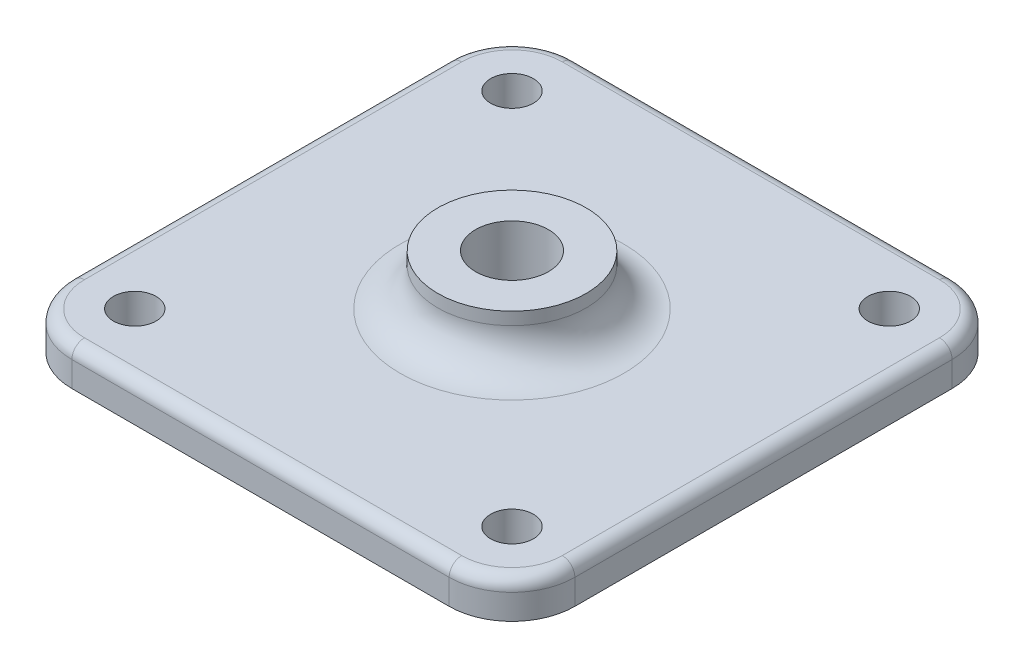
SolidWorks part; units mm, degrees
ref_plane "Front" through (0, 0, 0) normal (0, 0, 1) x (1, 0, 0)
ref_plane "Top" through (0, 0, 0) normal (0, 1, 0) x (1, 0, 0)
ref_plane "Right" through (0, 0, 0) normal (1, 0, 0) x (0, 0, -1)
sketch "Sketch1" plane through (0, 0, 0) normal (0, 1, 0) x (1, 0, 0)
  line L0 (-15, 15) -> (15, 15) construction
  line L1 (-15, -20) -> (15, -20)
  line L2 (-20, -15) -> (-20, 15)
  line L3 (-15, 20) -> (15, 20)
  line L4 (20, -15) -> (20, 15)
  line L5 (-20, -20) -> (20, 20) construction
  line L6 (-20, 20) -> (20, -20) construction
  line L7 (-50, 0) -> (50, 0) construction
  circle A2 centre (-15, 15) radius 1.7
  circle A3 centre (15, 15) radius 1.7
  circle A4 centre (15, -15) radius 1.7
  circle A5 centre (-15, -15) radius 1.7
  arc A6 (15, 20) -> (20, 15) centre (15, 15) cw
  arc A7 (20, -15) -> (15, -20) centre (15, -15) cw
  arc A8 (-15, -20) -> (-20, -15) centre (-15, -15) cw
  arc A9 (-20, 15) -> (-15, 20) centre (-15, 15) cw
  circle A10 centre (0, 0) radius 2.9
  circle A12 centre (0, 0) radius 5.9
  dimension "D5" = 3.4
  dimension "D6" = 3.4
  dimension "D8" = 5
  dimension "D1" = 5.8
  dimension "D3" = 40
  dimension "D4" = 40
  dimension "D7" = 30
  dimension "D2" = 3
extrude "Boss-Extrude1" add sketch "Sketch1" along normal blind 4 contours A12 A10 region at (-5.7331, 0, 0)
extrude "Boss-Extrude2" add sketch "Sketch1<3>" against normal blind 3 contours A12 A10 | A9 L2 A8 L1 A7 L4 A6 L3 A12 A4 A3 A2 A5 region at (-18.1355, 0, 18.1355) region at (-5.7331, 0, 0)
sketch "Sketch1<3>" plane through (0, 0, 0) normal (0, 1, 0) x (1, 0, 0) same geometry as "Sketch1"
fillet "Fillet1" radius 3 1 edges at (0, 0, 5.9)
fillet "Fillet2" radius 1 8 edges at (-18.5355, 0, -18.5355) (-20, 0, 0) (-18.5355, 0, 18.5355) (0, 0, 20) (18.5355, 0, 18.5355) (20, 0, 0) (18.5355, 0, -18.5355) (0, 0, -20)
equation "\"D5@Sketch1\"=\"D6@Sketch1\""
